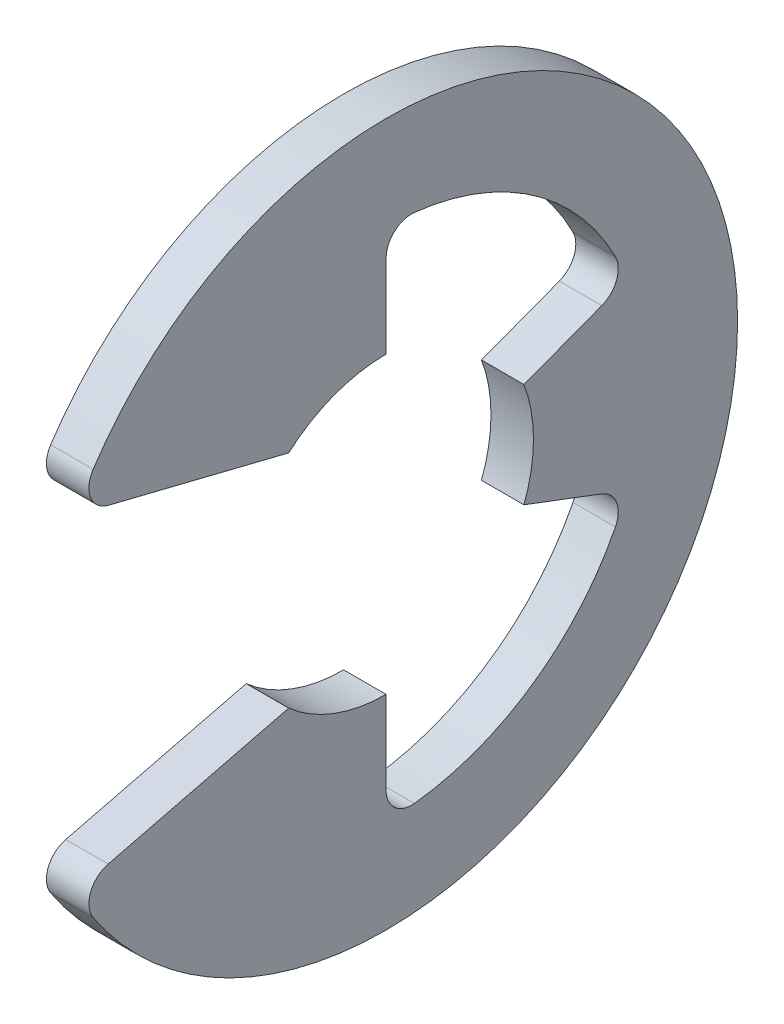
SolidWorks part; units mm, degrees
ref_plane "Front" through (0, 0, 0) normal (0, 0, 1) x (1, 0, 0)
ref_plane "Top" through (0, 0, 0) normal (0, 1, 0) x (1, 0, 0)
ref_plane "Right" through (0, 0, 0) normal (1, 0, 0) x (0, 0, -1)
sketch "Sketch1" plane through (0, 0, 0) normal (1, 0, 0) x (0, 0, -1)
  line L0 (-8.0547, -4.2345) -> (-2.5234, -2.8613)
  line L1 (-8.0547, 4.2345) -> (-2.5234, 2.8613)
  line L2 (0, -3.815) -> (0, -6.6658)
  line L3 (0, 3.815) -> (0, 6.6658)
  line L4 (3.5686, -1.3488) -> (6.2353, -2.3567)
  line L5 (3.5686, 1.3488) -> (6.2353, 2.3567)
  line L6 (0, 0) -> (-9.4, 0) construction
  line L7 (3.5686, 1.3488) -> (3.5686, -1.3488) construction
  line L8 (0, -3.815) -> (-2.5234, -2.8613) construction
  circle A1 centre (0, 0) radius 9.4 construction
  circle A2 centre (0, 0) radius 3.815 construction
  arc A3 (-8.0547, -4.2345) -> (-8.0547, 4.2345) centre (0, 0) ccw
  arc A4 (-2.5234, -2.8613) -> (0, -3.815) centre (0, 0) ccw
  arc A5 (-2.5234, 2.8613) -> (0, 3.815) centre (0, 0) cw
  arc A6 (3.5686, 1.3488) -> (3.5686, -1.3488) centre (0, 0) cw
  arc A7 (0, -6.6658) -> (6.2353, -2.3567) centre (0, 0) ccw
  arc A8 (6.2353, 2.3567) -> (0, 6.6658) centre (0, 0) ccw
  dimension "D" = 7.63
  dimension "D1" = 6.6658
  dimension "OD" = 18.2
  dimension "D2" = 4.3379
  dimension "D3" = 5.7225
extrude "Extrude1" add sketch "Sketch1" along normal mid plane 1.1
fillet "Fillet1" radius 0.66 6 edges at (0, -6.6658, 0) (0, 6.6658, 0) (0, -4.2345, 8.0547) (0, 4.2345, 8.0547) (0, -2.3567, -6.2353) (0, 2.3567, -6.2353)
sketch "Sketch3" plane through (0, 0, 0) normal (0, 1, 0) x (1, 0, 0)
  line L0 (0.575, 5) -> (0.575, 4.5)
  line L1 (0.575, 4.5) -> (-0.575, 4.5)
  line L2 (-0.575, 4.5) -> (-0.575, 5)
  line L3 (-0.575, 5) -> (-8.05, 5)
  line L4 (3.45, 0) -> (3.45, 4.75)
  line L5 (-8.05, 5) -> (-8.05, 0)
  line L6 (-8.05, 0) -> (3.45, 0)
  line L8 (3.45, 0) -> (3.45, 5) construction
  line L9 (3.45, 5) -> (0.575, 5) construction
  line L10 (3.45, 0) -> (17.2631, 0) construction
  line L11 (3.45, 4.75) -> (3.2, 5)
  line L12 (3.2, 5) -> (0.575, 5)
  point P2 (0, 4.5)
  point P5 (0.575, 4.75)
  dimension "D2" = 11.5
  dimension "D1" = 2.875
  dimension "D3" = 45
revolve "Revolve2" [suppressed] add sketch "Sketch3" angle 360 about L10
equation "\"D2@Sketch3\" = \"W@Sketch3\"*10"
equation "\"D1@Sketch3\" = \"D2@Sketch3\"/4"
equation "\"D1@Sketch1\" = (\"OD@Sketch1\"+\"D@Sketch1\")/3.875"
equation "\"D3@Sketch1\" = \"D@Sketch1\"*.75"
equation "\"D1@Fillet1\" = \"D1@Extrude1\"*.6"
